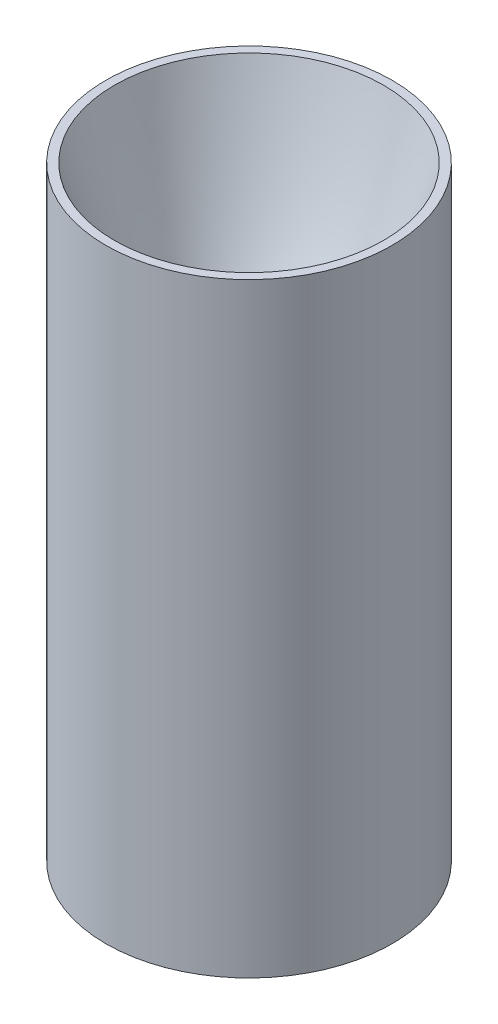
SolidWorks part; units mm, degrees
ref_plane "Front Plane" through (0, 0, 0) normal (0, 0, 1) x (1, 0, 0)
ref_plane "Top Plane" through (0, 0, 0) normal (0, 1, 0) x (1, 0, 0)
ref_plane "Right Plane" through (0, 0, 0) normal (1, 0, 0) x (0, 0, -1)
sketch "Sketch1" plane through (0, 0, 0) normal (0, 0, 1) x (1, 0, 0)
  line L0 (24.01, 0) -> (0, 0) construction
  line L1 (71.6385, 109.9273) -> (76.2, 109.9273)
  line L4 (53.7925, -59.7277) -> (53.7925, -212.1277)
  line L9 (76.2, 109.9273) -> (76.2, -212.1277)
  line L10 (76.2, -212.1277) -> (53.7925, -212.1277)
  line L11 (0, 0) -> (0, -107.6606) construction
  spline S0 degree 2 poles (26.7062, 6.5092) (49.1723, 34.636) (71.6385, 109.9273) knots 0 0 0 1 1 1 construction
  spline S1 degree 2 poles (26.7062, 6.5092) (49.1723, 34.636) (71.6385, 109.9273) knots 0 0 0 1 1 1
  spline S2 degree 4 poles (24.0378, -0.7181) (24.0369, -0.702) (24.0352, -0.674) (24.0319, -0.6548) (24.026, -0.5168) (24.0168, -0.4371) (24.0103, -0.1068) (24.0089, 0.0016) (24.013, 0.2676) (24.0194, 0.4271) (24.0315, 0.6468) (24.0524, 0.9014) (24.0861, 1.2025) (24.1374, 1.5421) (24.2015, 1.881) (24.2781, 2.2164) (24.3673, 2.5492) (24.4687, 2.8781) (24.5826, 3.2033) (24.7081, 3.5236) (24.8462, 3.8397) (24.995, 4.1493) (25.1569, 4.4548) (25.3274, 4.7513) (25.5134, 5.0457) (25.7027, 5.3255) (25.9153, 5.6107) (26.0898, 5.8329) (26.2773, 6.05) (26.4155, 6.2086) (26.6679, 6.4727) (26.7479, 6.5524) (27.0125, 6.8058) (27.099, 6.8781) (27.1963, 6.9666) (27.2147, 6.9802) (27.2373, 7.0002) knots 0 0 0 0 0 0.005192 0.010384 0.020768 0.041536 0.082569 0.102427 0.122284 0.142142 0.162 0.201716 0.241431 0.281147 0.320863 0.360578 0.400294 0.44001 0.479725 0.519441 0.559156 0.598872 0.638588 0.678303 0.718019 0.757735 0.79745 0.837166 0.857024 0.876882 0.916597 0.958047 0.979024 0.989512 1 1 1 1 1 construction
  spline S3 degree 4 poles (24.01, 0) (24.01, 0.0359) (24.0105, 0.1101) (24.013, 0.2676) (24.0194, 0.4271) (24.0315, 0.6468) (24.0524, 0.9014) (24.0861, 1.2025) (24.1374, 1.5421) (24.2015, 1.881) (24.2781, 2.2164) (24.3673, 2.5492) (24.4687, 2.8781) (24.5826, 3.2033) (24.7081, 3.5236) (24.8462, 3.8397) (24.995, 4.1493) (25.1569, 4.4548) (25.3274, 4.7513) (25.5134, 5.0457) (25.7027, 5.3255) (25.9153, 5.6107) (26.0898, 5.8329) (26.2773, 6.05) (26.4155, 6.2086) (26.5814, 6.3821) (26.6555, 6.4585) (26.7062, 6.5092) knots 0.082569 0.082569 0.082569 0.082569 0.082569 0.102427 0.122284 0.142142 0.162 0.201716 0.241431 0.281147 0.320863 0.360578 0.400294 0.44001 0.479725 0.519441 0.559156 0.598872 0.638588 0.678303 0.718019 0.757735 0.79745 0.837166 0.857024 0.876882 0.916597 0.916597 0.916597 0.916597 0.916597
  spline S4 degree 4 poles (24.1192, 2.8078) (24.1123, 2.7164) (24.0991, 2.5516) (24.0751, 2.1752) (24.0462, 1.6879) (24.0258, 1.1016) (24.0139, 0.6554) (24.0097, 0.1102) (24.0097, -0.1001) (24.0129, -0.5432) (24.0192, -0.8242) (24.0287, -1.1948) (24.0414, -1.5134) (24.0572, -1.8619) (24.0761, -2.1937) (24.1038, -2.6181) (24.1432, -3.122) (24.2142, -3.88) (24.3341, -4.8865) (24.5104, -6.0567) (24.7618, -7.3852) (25.0627, -8.7036) (25.4127, -10.0096) (25.8113, -11.3018) (26.2579, -12.5781) (26.7519, -13.8369) (27.2926, -15.0762) (27.8794, -16.2946) (28.5111, -17.4899) (29.1875, -18.6613) (29.9064, -19.8057) (30.669, -20.9239) (31.3701, -21.8744) (31.9997, -22.6734) (32.5351, -23.3204) (32.9832, -23.84) (33.4194, -24.3298) (33.8468, -24.7885) (34.1565, -25.1139) (34.523, -25.486) (34.677, -25.64) (35.0618, -26.0189) (35.3885, -26.3288) (35.8159, -26.7274) (36.1505, -27.0244) (36.4301, -27.2709) (36.5574, -27.38) (36.6257, -27.4388) (36.6605, -27.4687) knots 0 0 0 0 0 0.010393 0.020785 0.041571 0.062104 0.072371 0.082638 0.092575 0.102512 0.112449 0.122387 0.132324 0.142261 0.152198 0.162135 0.18201 0.201884 0.241633 0.281382 0.32113 0.360879 0.400628 0.440377 0.480126 0.519874 0.559623 0.599372 0.639121 0.67887 0.718618 0.758367 0.798116 0.81799 0.837865 0.857739 0.877613 0.897488 0.907425 0.917362 0.927629 0.937896 0.958429 0.979215 0.989607 0.994804 1 1 1 1 1 construction
  spline S5 degree 4 poles (24.01, 0) (24.01, -0.0705) (24.0105, -0.2136) (24.0129, -0.5432) (24.0192, -0.8242) (24.0287, -1.1948) (24.0414, -1.5134) (24.0572, -1.8619) (24.0761, -2.1937) (24.1038, -2.6181) (24.1432, -3.122) (24.2142, -3.88) (24.3341, -4.8865) (24.5104, -6.0567) (24.7618, -7.3852) (25.0627, -8.7036) (25.4127, -10.0096) (25.8113, -11.3018) (26.2579, -12.5781) (26.7519, -13.8369) (27.2926, -15.0762) (27.8794, -16.2946) (28.5111, -17.4899) (29.1875, -18.6613) (29.9064, -19.8057) (30.669, -20.9239) (31.3701, -21.8744) (31.9997, -22.6734) (32.5351, -23.3204) (32.9832, -23.84) (33.4194, -24.3298) (33.8468, -24.7885) (34.1565, -25.1139) (34.4478, -25.4096) (34.5473, -25.5099) (34.5972, -25.5598) knots 0.082638 0.082638 0.082638 0.082638 0.082638 0.092575 0.102512 0.112449 0.122387 0.132324 0.142261 0.152198 0.162135 0.18201 0.201884 0.241633 0.281382 0.32113 0.360879 0.400628 0.440377 0.480126 0.519874 0.559623 0.599372 0.639121 0.67887 0.718618 0.758367 0.798116 0.81799 0.837865 0.857739 0.877613 0.897488 0.907425 0.917362 0.917362 0.917362 0.917362 0.917362
  spline S6 degree 1 poles (34.5972, -25.5598) (43.2048, -34.1675) knots 0 0 1 1 construction
  spline S7 degree 1 poles (34.5972, -25.5598) (43.2048, -34.1675) knots 0 0 1 1
  spline S8 degree 4 poles (53.6833, -62.5354) (53.6902, -62.4466) (53.7033, -62.2738) (53.7213, -62.0018) (53.7419, -61.6601) (53.7589, -61.2922) (53.7725, -60.9659) (53.7826, -60.5754) (53.7894, -60.2941) (53.7927, -59.8333) (53.7927, -59.6305) (53.7896, -59.1817) (53.7832, -58.905) (53.7737, -58.5327) (53.7611, -58.213) (53.7414, -57.7818) (53.7113, -57.2811) (53.6671, -56.6882) (53.5882, -55.8486) (53.4884, -55.0083) (53.3676, -54.1726) (53.1977, -53.1726) (53.003, -52.1776) (52.7773, -51.1887) (52.5209, -50.2076) (52.2402, -49.2332) (51.9353, -48.2661) (51.5445, -47.1493) (51.0505, -45.8906) (50.5097, -44.6511) (49.923, -43.4329) (49.2911, -42.2373) (48.6151, -41.0663) (47.8954, -39.9211) (47.134, -38.8042) (46.4308, -37.8516) (45.8045, -37.0558) (45.2637, -36.4035) (44.8261, -35.8944) (44.4257, -35.4472) (44.0924, -35.0848) (43.7849, -34.7605) (43.585, -34.5517) (43.2762, -34.2384) (43.1268, -34.0891) (42.7386, -33.7068) (42.415, -33.3999) (41.985, -32.9988) (41.6521, -32.7035) (41.3716, -32.4561) (41.2447, -32.3474) (41.1763, -32.2885) (41.1415, -32.2585) knots 0 0 0 0 0 0.010393 0.020785 0.031178 0.041571 0.051838 0.062104 0.072371 0.082638 0.092575 0.102512 0.112449 0.122387 0.132324 0.142261 0.162135 0.18201 0.201884 0.241633 0.261507 0.281382 0.32113 0.360879 0.380754 0.400628 0.440377 0.480126 0.519874 0.559623 0.599372 0.639121 0.67887 0.718618 0.758367 0.798116 0.81799 0.837865 0.857739 0.877613 0.887551 0.897488 0.907425 0.917362 0.927629 0.937896 0.958429 0.979215 0.989607 0.994804 1 1 1 1 1 construction
  spline S9 degree 4 poles (53.7925, -59.7277) (53.7925, -59.6571) (53.7919, -59.5156) (53.7896, -59.1817) (53.7832, -58.905) (53.7737, -58.5327) (53.7611, -58.213) (53.7414, -57.7818) (53.7113, -57.2811) (53.6671, -56.6882) (53.5882, -55.8486) (53.4884, -55.0083) (53.3676, -54.1726) (53.1977, -53.1726) (53.003, -52.1776) (52.7773, -51.1887) (52.5209, -50.2076) (52.2402, -49.2332) (51.9353, -48.2661) (51.5445, -47.1493) (51.0505, -45.8906) (50.5097, -44.6511) (49.923, -43.4329) (49.2911, -42.2373) (48.6151, -41.0663) (47.8954, -39.9211) (47.134, -38.8042) (46.4308, -37.8516) (45.8045, -37.0558) (45.2637, -36.4035) (44.8261, -35.8944) (44.4257, -35.4472) (44.0924, -35.0848) (43.7849, -34.7605) (43.585, -34.5517) (43.3553, -34.3187) (43.2547, -34.2173) (43.2048, -34.1675) knots 0.082638 0.082638 0.082638 0.082638 0.082638 0.092575 0.102512 0.112449 0.122387 0.132324 0.142261 0.162135 0.18201 0.201884 0.241633 0.261507 0.281382 0.32113 0.360879 0.380754 0.400628 0.440377 0.480126 0.519874 0.559623 0.599372 0.639121 0.67887 0.718618 0.758367 0.798116 0.81799 0.837865 0.857739 0.877613 0.887551 0.897488 0.907425 0.917362 0.917362 0.917362 0.917362 0.917362
  spline S10 degree 2 poles (36.8348, 6.4922) (58.5836, 47.0333) (81.7275, 109.9275) knots 0.442127 0.442127 0.442127 0.998319 0.998319 0.998319 construction
  dimension "D1" = 152.4
  dimension "D2" = 24.01
  dimension "D3" = 152.4
revolve "Revolve2" add sketch "Sketch1" angle 360 about L11
hole_wizard "3/8-24 Tapped Hole1" positions "Sketch3" profile "Sketch4" tap size "3/8-24" standard "ANSI Inch"
sketch "Sketch3" plane through (0, -212.1277, 0) normal (0, -1, 0) x (-1, 0, 0)
  circle A1 centre (0, 0) radius 66.675 construction
  point P10 (-66.675, 0)
  dimension "D1" = 133.35
sketch "Sketch4" plane through (66.675, -212.1277, 0) normal (1, 0, 0) x (0, 0, -1)
  line L0 (0, 0) -> (0, 27.5347)
  line L1 (0, 27.5347) -> (4.2164, 25.0012)
  line L2 (4.2164, 25.0012) -> (4.2164, 0)
  line L5 (4.2164, 0) -> (0, 0)
  line L10 (0, 27.5347) -> (-4.2164, 25.0012) construction
  line L11 (0, -6.35) -> (0, 107.95) construction
  dimension "Tap Drill Dia." = 8.4328
  dimension "Tap Drill Depth" = 25.0012
  dimension "Drill Angle" = 118
cosmetic thread "Hole Thread1" parameters "D1"=20, "D2"=9.525
pattern_circular "CirPattern1" count 8 over 360 of "3/8-24 Tapped Hole1"
cosmetic thread "Hole Thread2" parameters "D1"=20, "D2"=9.525
cosmetic thread "Hole Thread3" parameters "D1"=20, "D2"=9.525
cosmetic thread "Hole Thread4" parameters "D1"=20, "D2"=9.525
cosmetic thread "Hole Thread5" parameters "D1"=20, "D2"=9.525
cosmetic thread "Hole Thread6" parameters "D1"=20, "D2"=9.525
cosmetic thread "Hole Thread7" parameters "D1"=20, "D2"=9.525
cosmetic thread "Hole Thread8" parameters "D1"=20, "D2"=9.525
sketch "Sketch8" [suppressed] plane through (0, -212.1275, 0) normal (0, -1, 0) x (1, 0, 0)
  circle A0 centre (0, 0) radius 53.8815 construction
  circle A1 centre (0, 0) radius 76.49 construction
  circle A2 centre (0, 0) radius 65.2002 construction
  dimension "D1" = 107.7631
  dimension "D2" = 130.4004
  dimension "D3" = 152.98
sketch "Sketch9" plane through (0, -212.1277, 0) normal (0, -1, 0) x (1, 0, 0)
  circle A0 centre (0, 0) radius 53.8815
  circle A1 centre (0, 0) radius 56.8815
  dimension "D1" = 3
extrude "Cut-Extrude1" [suppressed] cut sketch "Sketch9" against normal blind 6
hole_wizard "1/4 (0.2500) Dowel Hole1" positions "Sketch11" profile "Sketch12" hole size "1/4" standard "ANSI Inch"
sketch "Sketch11" plane through (0, -212.1277, 0) normal (0, -1, 0) x (-1, 0, 0)
  line L6 (0, 0) -> (61.5997, -25.5154) construction
  line L8 (0, 0) -> (-61.5997, 25.5154) construction
  line L9 (0, 0) -> (-66.675, 0) construction
  circle A0 centre (0, 0) radius 66.675 construction
  point P22 (61.5997, -25.5154)
  point P28 (-61.5997, 25.5154)
  dimension "D1" = 22.5
sketch "Sketch12" plane through (61.5997, -212.1277, -25.5154) normal (1, 0, 0) x (0, 0, -1)
  line L0 (0, 0) -> (0, 11.8137)
  line L1 (0, 11.8137) -> (3.175, 9.906)
  line L2 (3.175, 9.906) -> (3.175, 0)
  line L5 (3.175, 0) -> (0, 0)
  line L10 (0, 11.8137) -> (-3.175, 9.906) construction
  line L11 (0, -6.35) -> (0, 107.95) construction
  dimension "Hole Dia." = 6.35
  dimension "Hole Depth" = 9.906
  dimension "Drill Angle" = 118
sketch "Sketch14" plane through (0, -212.1277, 0) normal (0, -1, 0) x (1, 0, 0)
  circle A0 centre (0, 0) radius 53.7925 construction
  circle A1 centre (0, 0) radius 53.7925 construction
  circle A2 centre (0, 0) radius 55.38
  circle A3 centre (0, 0) radius 57.412
  dimension "D1" = 1.5875
  dimension "D2" = 2.032
extrude "gasket_groove" [suppressed] cut sketch "Sketch14" against normal blind 1.27
